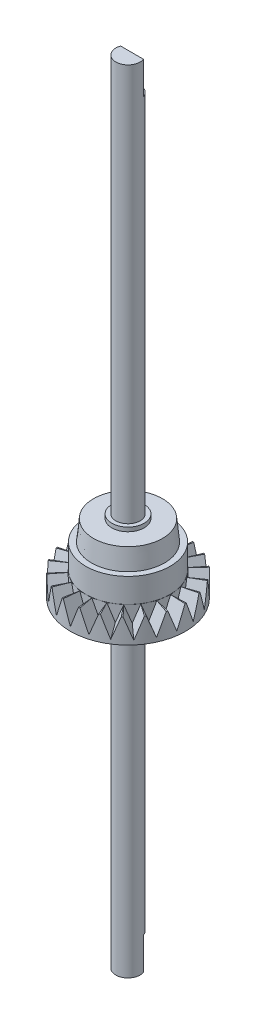
SolidWorks part; units mm, degrees
ref_plane "Ön Düzlem" through (0, 0, 0) normal (0, 0, 1) x (1, 0, 0)
ref_plane "Üst Düzlem" through (0, 0, 0) normal (0, 1, 0) x (1, 0, 0)
ref_plane "Sağ Düzlem" through (0, 0, 0) normal (1, 0, 0) x (0, 0, -1)
sketch "Sketch2" plane through (0, 0, 0) normal (0, 1, 0) x (1, 0, 0)
  circle A0 centre (0, 0) radius 1.5
  dimension "D1" = 3
extrude "Boss-Extrude1" add sketch "Sketch2" along normal blind 37.5
sketch "Sketch3" plane through (0, 37.5, 0) normal (0, 1, 0) x (1, 0, 0)
  circle A0 centre (0, 0) radius 2.5
  dimension "D1" = 5
extrude "Boss-Extrude2" add sketch "Sketch3" along normal blind 2 separate body
sketch "Sketch4" plane through (0, 39.5, 0) normal (0, 1, 0) x (1, 0, 0)
  circle A0 centre (0, 0) radius 7.1
  dimension "D1" = 14.2
extrude "Boss-Extrude3" add sketch "Sketch4" along normal blind 3
sketch "Sketch5" plane through (0, 42.5, 0) normal (0, 1, 0) x (1, 0, 0)
  circle A1 centre (0, 0) radius 5.2
  dimension "D1" = 10.4
extrude "Boss-Extrude4" add sketch "Sketch5" along normal blind 3 separate body
sketch "Sketch6" plane through (0, 45.5, 0) normal (0, 1, 0) x (1, 0, 0)
  circle A0 centre (0, 0) radius 4.5
  dimension "D1" = 9
ref_plane "Plane2" through (0, 48, 0) normal (0, 1, 0) x (1, 0, 0)
sketch "Sketch7" plane through (0, 48, 0) normal (0, 1, 0) x (1, 0, 0)
  circle A0 centre (0, 0) radius 4.25
  dimension "D1" = 8.5
loft "Loft1" add profiles "Sketch6", "Sketch7" connector at (-3.2881, 45.5, 3.0722) connector at (-2.6531, 48, 3.3202)
sketch "Sketch8" plane through (0, 48, 0) normal (0, 1, 0) x (1, 0, 0)
  circle A0 centre (0, 0) radius 2
  dimension "D1" = 4
extrude "Boss-Extrude5" add sketch "Sketch8" along normal blind 0.5
sketch "Sketch9" plane through (0, 48.5, 0) normal (0, 1, 0) x (1, 0, 0)
  circle A0 centre (0, 0) radius 1.5
  dimension "D1" = 3
extrude "Boss-Extrude6" add sketch "Sketch9" along normal blind 49
sketch "Sketch10" plane through (0, 0, 0) normal (0, 1, 0) x (1, 0, 0)
  line L0 (-1.4142, 0.5) -> (1.4142, 0.5)
  line L1 (0, 1.5) -> (0, 0.5) construction
  arc A0 (1.4142, 0.5) -> (-1.4142, 0.5) centre (0, 0) ccw
  dimension "D1" = 3
  dimension "D2" = 1
extrude "Cut-Extrude1" cut sketch "Sketch10" along normal blind 4
sketch "Sketch11" plane through (0, 97.5, 0) normal (0, 1, 0) x (1, 0, 0)
  line L0 (-1.4142, 0.5) -> (1.4142, 0.5)
  line L1 (0, 0.5) -> (0, 1.5) construction
  arc A0 (1.4142, 0.5) -> (-1.4142, 0.5) centre (0, 0) ccw
  dimension "D1" = 3
  dimension "D2" = 1
extrude "Cut-Extrude2" cut sketch "Sketch11" against normal blind 4
ref_plane "Plane3" through (0, 0, 7.1) normal (0, 0, 1) x (1, 0, 0)
sketch "Sketch12" plane through (0, 0, 7.1) normal (0, 0, 1) x (1, 0, 0)
  line L0 (0, 40) -> (-0.75, 42)
  line L2 (0.75, 42) -> (0, 40)
  line L3 (-0.75, 42) -> (-0.9375, 42.5)
  line L4 (-2.5, 39.5) -> (2.5, 39.5) construction
  line L5 (7.1, 42.5) -> (-7.1, 42.5) construction
  line L7 (-7.1, 39.5) -> (7.1, 39.5) construction
  line L8 (0.75, 42) -> (0.9375, 42.5)
  line L9 (-0.9375, 42.5) -> (0.9375, 42.5)
  dimension "D1" = 2.5
  dimension "D2" = 0.5
  dimension "D3" = 1.5
ref_plane "Plane4" through (0, 0, 5.2) normal (0, 0, 1) x (1, 0, 0)
sketch "Sketch13" plane through (0, 0, 5.2) normal (0, 0, 1) x (1, 0, 0)
  line L1 (0, 40) -> (-0.75, 42) construction
  line L2 (0.75, 42) -> (0, 40) construction
  line L3 (-0.75, 42) -> (0.75, 42) construction
  line L4 (0, 40) -> (-0.75, 42) construction
  line L5 (0.75, 42) -> (0, 40) construction
  line L6 (0, 40.5) -> (-0.75, 42.5)
  line L7 (-0.75, 42.5) -> (0.75, 42.5)
  line L8 (0.75, 42.5) -> (0, 40.5)
  line L10 (7.1, 42.5) -> (-7.1, 42.5) construction
  dimension "D1" = 2
loft "Cut-Loft8" cut profiles "Sketch12", "Sketch13" connector at (0, 40, 7.1) connector at (0, 40.5, 5.2)
pattern_circular "CirPattern2" count 22 over 360 about axis through (0, 42.5, 0) along (0, -1, 0) of "Cut-Loft8"
